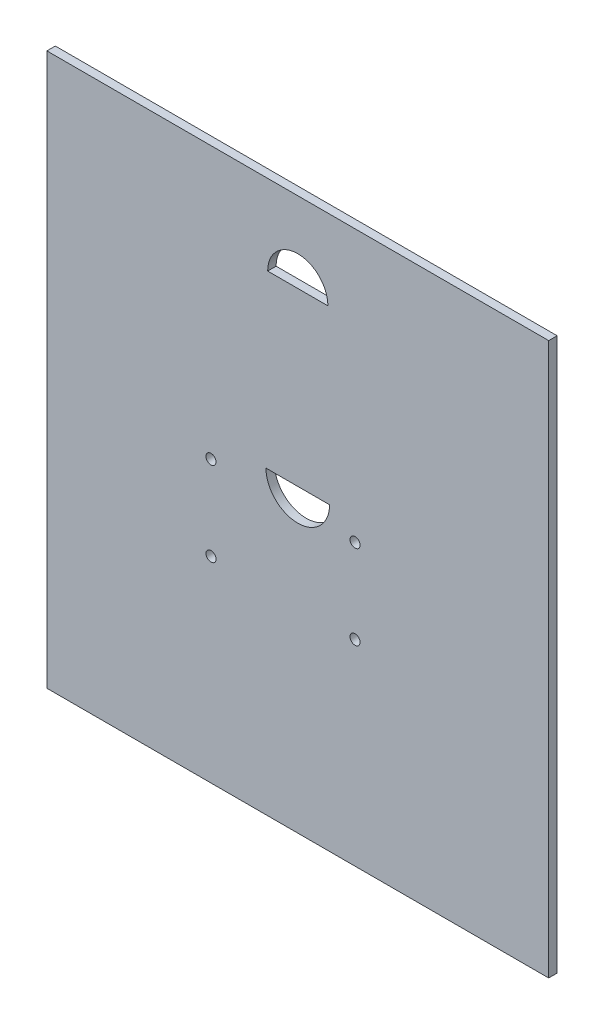
SolidWorks part; units mm, degrees
ref_plane "Plan de face" through (0, 0, 0) normal (0, 0, 1) x (1, 0, 0)
ref_plane "Plan de dessus" through (0, 0, 0) normal (0, 1, 0) x (1, 0, 0)
ref_plane "Plan de droite" through (0, 0, 0) normal (1, 0, 0) x (0, 0, -1)
sketch "Sketch1" plane through (0, 0, 0) normal (0, 0, 1) x (1, 0, 0)
  line L1 (-220.2282, 110.1141) -> (29.7718, 110.1141)
  line L2 (-220.2282, 110.1141) -> (-220.2282, -164.8859)
  line L3 (-220.2282, -164.8859) -> (29.7718, -164.8859)
  line L4 (29.7718, 110.1141) -> (29.7718, -164.8859)
  dimension "D1" = 275
  dimension "D2" = 250
extrude "Boss-Extrude1" add sketch "Sketch1" along normal blind 4.2
sketch "Esquisse1" plane through (0, 0, 4.2) normal (0, 0, 1) x (1, 0, 0)
  line L0 (-220.2282, 110.1141) -> (-220.2282, -164.8859) construction
  line L1 (-110.2282, 70.1141) -> (-80.2282, 70.1141)
  line L2 (29.7718, 110.1141) -> (-220.2282, 110.1141) construction
  line L5 (-111.0739, -15.3059) -> (-79.3825, -15.3059)
  arc A1 (-110.2282, 70.1141) -> (-80.2282, 70.1141) centre (-95.2282, 70.1141) cw
  arc A3 (-111.0739, -15.3059) -> (-79.3825, -15.3059) centre (-95.2282, -15.3059) ccw
  circle A4 centre (-66.7074, -67.065) radius 2.5
  circle A5 centre (-66.7074, -25.155) radius 2.5
  circle A6 centre (-138.4624, -67.065) radius 2.5
  circle A7 centre (-138.4624, -25.155) radius 2.5
  dimension "D2" = 15
  dimension "D4" = 85.42
  dimension "D1" = 125
  dimension "D3" = 40
  dimension "D5" = 0
  dimension "D6" = 41.91
  dimension "D7" = 71.755
  dimension "D8" = 41.91
  dimension "D9" = 71.755
  dimension "D10" = 83.0977
  dimension "D11" = 83.0977
extrude "Enlèv. mat.-Extru.1" cut sketch "Esquisse1" against normal through all
